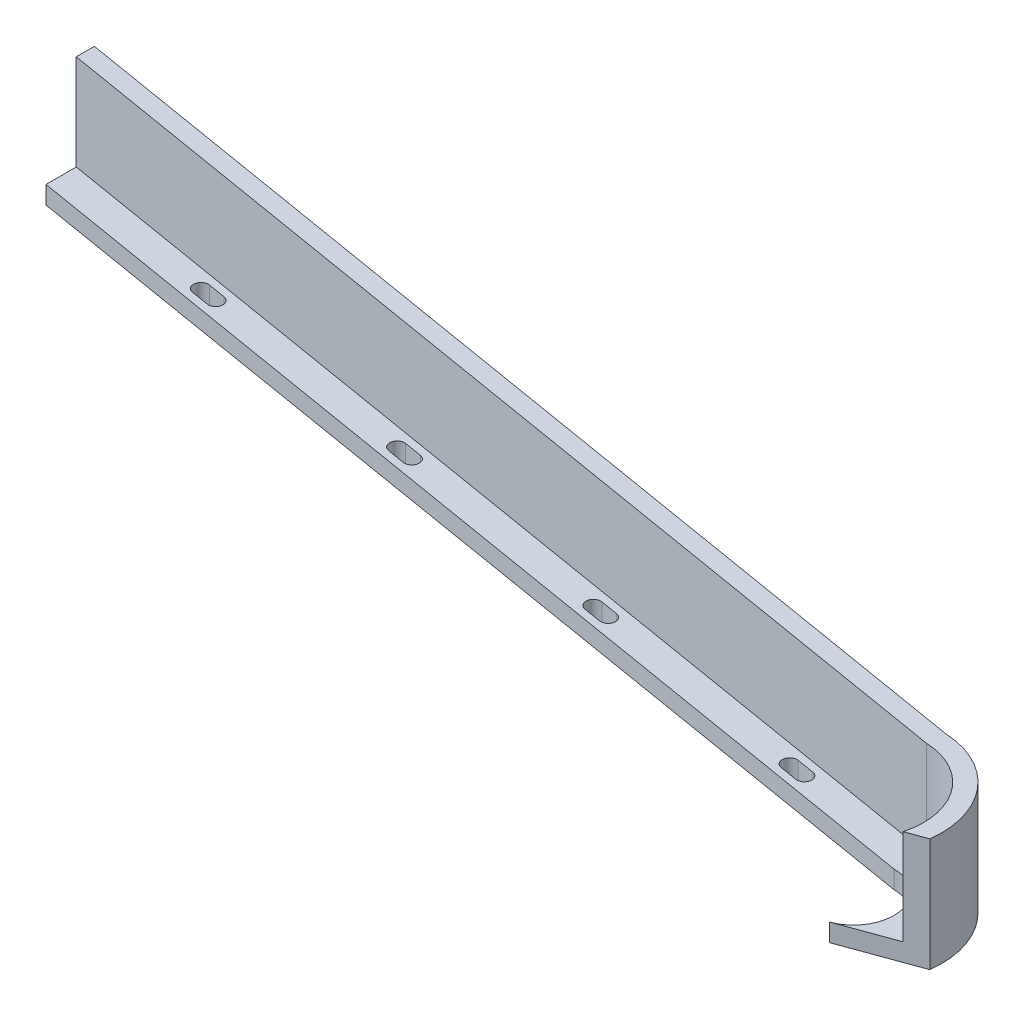
SolidWorks part; units mm, degrees
ref_plane "前视基准面" through (0, 0, 0) normal (0, 0, 1) x (1, 0, 0)
ref_plane "上视基准面" through (0, 0, 0) normal (0, 1, 0) x (1, 0, 0)
ref_plane "右视基准面" through (0, 0, 0) normal (1, 0, 0) x (0, 0, -1)
sketch "草图1" plane through (0, 0, 0) normal (0, 1, 0) x (1, 0, 0)
  line L1 (-17.5, -27.5) -> (17.5, -27.5)
  line L2 (-17.5, -27.5) -> (-17.5, 27.5)
  line L3 (-17.5, 27.5) -> (17.5, 27.5)
  line L4 (17.5, -27.5) -> (17.5, 27.5)
  line L5 (-17.5, -27.5) -> (17.5, 27.5) construction
  line L6 (-17.5, 27.5) -> (17.5, -27.5) construction
  point P0 (0, 0)
  dimension "D1" = 55
  dimension "D2" = 35
extrude "凸台-拉伸1" add sketch "草图1" along normal blind 1
sketch "草图2" plane through (0, 1, 0) normal (0, 1, 0) x (1, 0, 0)
  line L0 (-105.917, 0) -> (-62.25, 0) construction
  line L1 (106.75, 2.25) -> (121.75, 2.25)
  line L2 (-31.4474, 57.1013) -> (151.75, 26.6691)
  line L4 (124.0586, 2.6571) -> (154.0586, 13.5762)
  line L5 (-60.1618, 23.6059) -> (-42.6093, 52.0296)
  line L6 (121.75, 2.25) -> (121.75, 9) construction
  line L7 (121.75, -2.25) -> (121.75, -9) construction
  line L8 (-60.1618, -23.6059) -> (-42.6093, -52.0296)
  line L9 (124.0586, -2.6571) -> (154.0586, -13.5762)
  line L10 (121.75, -9) -> (128.5, -9)
  line L11 (-31.4474, -57.1013) -> (151.75, -26.6691)
  line L12 (106.75, -2.25) -> (121.75, -2.25)
  line L13 (-62.25, 16.25) -> (-62.25, -16.25)
  line L14 (106.75, 2.25) -> (106.75, -2.25)
  line L15 (106.75, 0) -> (124.0666, 0) construction
  arc A0 (-60.1618, 23.6059) -> (-62.25, 16.25) centre (-48.25, 16.25) ccw
  arc A1 (-31.4474, 57.1013) -> (-42.6093, 52.0296) centre (-33.25, 46.25) ccw
  arc A2 (121.75, 2.25) -> (124.0586, 2.6571) centre (121.75, 9) ccw
  arc A3 (154.0586, 13.5762) -> (151.75, 26.6691) centre (151.75, 19.9191) ccw
  arc A4 (154.0586, -13.5762) -> (151.75, -26.6691) centre (151.75, -19.9191) cw
  arc A5 (121.75, -2.25) -> (128.5, -9) centre (121.75, -9) cw
  arc A6 (-31.4474, -57.1013) -> (-42.6093, -52.0296) centre (-33.25, -46.25) cw
  arc A7 (-60.1618, -23.6059) -> (-62.25, -16.25) centre (-48.25, -16.25) cw
  line M10 (17.5, -27.5) -> (17.5, 27.5)
  line M11 (17.5, 27.5) -> (-17.5, 27.5)
  line M12 (-17.5, 27.5) -> (-17.5, -27.5)
  line M13 (-17.5, -27.5) -> (17.5, -27.5)
  dimension "D2" = 28
  dimension "D3" = 48.25
  dimension "D4" = 22
  dimension "D5" = 15
  dimension "D7" = 13.5
  dimension "D10" = 13.5
  dimension "D11" = 30
  dimension "D1" = 2.25
  dimension "D8" = 20
  dimension "D9" = 30
  dimension "D12" = 15
extrude "凸台-拉伸2" add sketch "草图2" along normal blind 3 contours A7 L8 A6 L11 A4 L9 A5 L12 L14 L1 A2 L4 A3 L2 A1 L5 A0 L13 | M13 M10 M11 M12 region at (37.3678, 1, 0) region at (0, 1, 0)
sketch "草图3" plane through (0, 4, 0) normal (0, 1, 0) x (1, 0, 0)
  circle A0 centre (-48.25, 16.25) radius 5
  circle A1 centre (-48.25, -16.25) radius 5
  circle A2 centre (-33.25, 46.25) radius 6.6982
  circle A3 centre (151.75, 19.9191) radius 2.5794
  circle A4 centre (121.75, 9) radius 2.5794
  circle A5 centre (121.75, -9) radius 2.5794
  circle A6 centre (151.75, -19.9191) radius 2.5794
  circle A7 centre (-33.25, -46.25) radius 6.6982
  dimension "D1" = 10
extrude "切除-拉伸1" cut sketch "草图3" against normal through all contours A0 | A1 region at (-48.25, 4, -16.25)
sketch "草图4" plane through (0, 4, 0) normal (0, 1, 0) x (1, 0, 0)
  circle A0 centre (-33.25, 46.25) radius 4
  circle A1 centre (-33.25, -46.25) radius 4
  dimension "D1" = 8
  dimension "D2" = 8
extrude "切除-拉伸2" cut sketch "草图4" against normal blind 2
sketch "草图5" plane through (0, 4, 0) normal (0, 1, 0) x (1, 0, 0)
  circle A0 centre (121.75, 9) radius 2
  circle A1 centre (121.75, -9) radius 2
  circle A2 centre (151.75, 19.9191) radius 2
  circle A3 centre (151.75, -19.9191) radius 2
  dimension "D1" = 4
extrude "切除-拉伸3" cut sketch "草图5" against normal blind 2
sketch "草图8" plane through (0, 1, 0) normal (0, -1, 0) x (1, 0, 0)
  line L1 (-39.75, -26.25) -> (-26.75, -26.25)
  line L2 (-39.75, -26.25) -> (-39.75, -66.25)
  line L3 (-39.75, -66.25) -> (-26.75, -66.25)
  line L4 (-26.75, -26.25) -> (-26.75, -66.25)
  line L5 (-39.75, -26.25) -> (-26.75, -66.25) construction
  line L6 (-39.75, -66.25) -> (-26.75, -26.25) construction
  line L16 (124.0586, 2.6571) -> (154.0586, 13.5762)
  line L17 (151.75, 26.6691) -> (-31.4474, 57.1013)
  line L18 (-42.6093, 52.0296) -> (-60.1618, 23.6059)
  line L19 (-62.25, 16.25) -> (-62.25, -16.25)
  line L20 (-60.1618, -23.6059) -> (-42.6093, -52.0296)
  line L21 (-31.4474, -57.1013) -> (151.75, -26.6691)
  line L22 (154.0586, -13.5762) -> (124.0586, -2.6571)
  line L23 (121.75, -2.25) -> (106.75, -2.25)
  line L24 (106.75, -2.25) -> (106.75, 2.25)
  line L25 (106.75, 2.25) -> (121.75, 2.25)
  line L26 (124.0586, 2.6571) -> (154.0586, 13.5762)
  line L27 (151.75, 26.6691) -> (-31.4474, 57.1013)
  line L28 (-42.6093, 52.0296) -> (-60.1618, 23.6059)
  line L31 (-31.4474, -57.1013) -> (151.75, -26.6691)
  line L32 (154.0586, -13.5762) -> (124.0586, -2.6571)
  line L33 (121.75, -2.25) -> (106.75, -2.25)
  line L34 (106.75, -2.25) -> (106.75, 2.25)
  line L35 (106.75, 2.25) -> (121.75, 2.25)
  arc A8 (154.0586, 13.5762) -> (151.75, 26.6691) centre (151.75, 19.9191) ccw
  arc A9 (-31.4474, 57.1013) -> (-42.6093, 52.0296) centre (-33.25, 46.25) ccw
  arc A10 (-60.1618, 23.6059) -> (-62.25, 16.25) centre (-48.25, 16.25) ccw
  arc A11 (-62.25, -16.25) -> (-60.1618, -23.6059) centre (-48.25, -16.25) ccw
  arc A12 (-42.6093, -52.0296) -> (-31.4474, -57.1013) centre (-33.25, -46.25) ccw
  arc A13 (151.75, -26.6691) -> (154.0586, -13.5762) centre (151.75, -19.9191) ccw
  arc A14 (124.0586, -2.6571) -> (121.75, -2.25) centre (121.75, -9) ccw
  arc A15 (121.75, 2.25) -> (124.0586, 2.6571) centre (121.75, 9) ccw
  arc A16 (154.0586, 13.5762) -> (151.75, 26.6691) centre (151.75, 19.9191) ccw
  arc A17 (-31.4474, 57.1013) -> (-42.6093, 52.0296) centre (-33.25, 46.25) ccw
  arc A18 (-60.1618, 23.6059) -> (-62.25, 16.25) centre (-48.25, 16.25) ccw
  arc A19 (-62.25, -16.25) -> (-60.1618, -23.6059) centre (-48.25, -16.25) ccw
  arc A20 (-42.6093, -52.0296) -> (-31.4474, -57.1013) centre (-33.25, -46.25) ccw
  arc A21 (151.75, -26.6691) -> (154.0586, -13.5762) centre (151.75, -19.9191) ccw
  arc A22 (124.0586, -2.6571) -> (121.75, -2.25) centre (121.75, -9) ccw
  arc A23 (121.75, 2.25) -> (124.0586, 2.6571) centre (121.75, 9) ccw
  point P0 (-33.25, -46.25)
  arc M32 (-42.6093, -52.0296) -> (-31.4474, -57.1013) centre (-33.25, -46.25) ccw
  line M33 (-31.4474, -57.1013) -> (151.75, -26.6691)
  dimension "D1" = 13
  dimension "D2" = 40
  dimension "D3" = 0
extrude "凸台-拉伸3" add sketch "草图8" along normal blind 7 contours L4 L1 L2 M32 M33 region at (-33.2258, 1, -41.4837)
mirror "镜向1" about plane through (0, 0, 0) normal (0, 0, 1) of "凸台-拉伸3"
sketch "草图9" plane through (0, -6, 0) normal (0, -1, 0) x (1, 0, 0)
  line L0 (-39.75, -26.25) -> (-26.75, -26.25) construction
  line L2 (-38.25, -53.75) -> (-38.25, -27.75)
  line L3 (-38.25, -27.75) -> (-28.25, -27.75)
  line L4 (-28.25, -53.75) -> (-28.25, -27.75)
  line L5 (-35.5448, -54.7408) -> (-28.25, -27.75) construction
  line L6 (-38.25, -27.75) -> (-31.223, -53.75) construction
  line L8 (-28.25, -53.75) -> (-38.25, -53.75)
  point P0 (-33.25, -46.25)
  dimension "D1" = 10
  dimension "D2" = 1.5
  dimension "D3" = 26
extrude "切除-拉伸4" cut sketch "草图9" against normal through all from offset 1.5 offset against normal yes
mirror "镜向2" about plane through (0, 0, 0) normal (0, 0, 1) of "切除-拉伸4"
sketch "草图10" plane through (0, 0, -53.75) normal (0, 0, 1) x (1, 0, 0)
  line L4 (-38.25, -4.5) -> (-28.25, -4.5)
  line L5 (-28.25, -4.5) -> (-28.25, 4)
  line L6 (-28.25, 4) -> (-38.25, 4)
  line L7 (-38.25, 4) -> (-38.25, -4.5)
  line L8 (-38.25, -4.5) -> (-28.25, -4.5)
  line L9 (-28.25, -4.5) -> (-28.25, 4)
  line L10 (-28.25, 4) -> (-38.25, 4)
  line L11 (-38.25, 4) -> (-38.25, -4.5)
  circle A0 centre (-33.25, -1.5) radius 1.5
  dimension "D2" = 3
  dimension "D3" = 3
  dimension "D1" = 0
extrude "切除-拉伸5" cut sketch "草图10" against normal through all contours A0 region at (-33.25, -1.5, -53.75)
mirror "镜向3" about plane through (0, 0, 0) normal (0, 0, 1) of "切除-拉伸5"
sketch "草图12" plane through (0, 4, 0) normal (0, 1, 0) x (1, 0, 0)
  line L3 (152.5362, 34.6481) -> (-30.1364, 64.9932)
  line L5 (-42.6093, 52.0296) -> (-60.1618, 23.6059) construction
  line L6 (124.0586, 2.6571) -> (154.0586, 13.5762) construction
  line L10 (154.0586, -13.5762) -> (124.0586, -2.6571)
  line L11 (121.75, -2.25) -> (106.75, -2.25)
  line L12 (106.75, -2.25) -> (106.75, 2.25)
  line L13 (106.75, 2.25) -> (121.75, 2.25)
  line L14 (124.0586, 2.6571) -> (154.0586, 13.5762)
  line L15 (151.75, 26.6691) -> (-31.4474, 57.1013)
  line L16 (-42.6093, 52.0296) -> (-60.1618, 23.6059)
  line L17 (-62.25, 16.25) -> (-62.25, -16.25)
  line L18 (-60.1618, -23.6059) -> (-42.6093, -52.0296)
  line L19 (-31.4474, -57.1013) -> (151.75, -26.6691)
  line L23 (-62.25, 2.25) -> (121.75, 2.25)
  line L24 (124.0586, 2.6571) -> (166.3826, 18.0617)
  line L26 (-34.4695, 65.2108) -> (-60.1618, 23.6059)
  line L27 (-62.25, 16.25) -> (-62.25, 2.25)
  line L30 (-49.416, 56.233) -> (-66.9685, 27.8093) construction
  line L31 (-70.25, 16.25) -> (-70.25, -5.75) construction
  line L32 (-70.25, -5.75) -> (121.75, -5.75) construction
  line L33 (126.7948, -4.8605) -> (156.7948, 6.0586) construction
  line L34 (151.75, 26.6691) -> (-31.4474, 57.1013) construction
  arc A1 (166.3826, 18.0617) -> (152.5362, 34.6481) centre (151.75, 19.9191) ccw
  arc A2 (-30.1364, 64.9932) -> (-34.4695, 65.2108) centre (-33.25, 46.25) ccw
  arc A4 (-30.1364, 64.9932) -> (-49.416, 56.233) centre (-33.25, 46.25) ccw construction
  arc A5 (156.7948, 6.0586) -> (152.5362, 34.6481) centre (151.75, 19.9191) ccw construction
  arc A8 (124.0586, -2.6571) -> (121.75, -2.25) centre (121.75, -9) ccw
  arc A9 (121.75, 2.25) -> (124.0586, 2.6571) centre (121.75, 9) ccw
  arc A10 (154.0586, 13.5762) -> (151.75, 26.6691) centre (151.75, 19.9191) ccw
  arc A11 (-31.4474, 57.1013) -> (-42.6093, 52.0296) centre (-33.25, 46.25) ccw
  arc A12 (-60.1618, 23.6059) -> (-62.25, 16.25) centre (-48.25, 16.25) ccw
  arc A13 (-62.25, -16.25) -> (-60.1618, -23.6059) centre (-48.25, -16.25) ccw
  arc A14 (-42.6093, -52.0296) -> (-31.4474, -57.1013) centre (-33.25, -46.25) ccw
  arc A15 (151.75, -26.6691) -> (154.0586, -13.5762) centre (151.75, -19.9191) ccw
  arc A17 (121.75, 2.25) -> (124.0586, 2.6571) centre (121.75, 9) ccw
  arc A20 (-60.1618, 23.6059) -> (-62.25, 16.25) centre (-48.25, 16.25) ccw
  arc A24 (-66.9685, 27.8093) -> (-70.25, 16.25) centre (-48.25, 16.25) ccw construction
  arc A25 (121.75, -5.75) -> (126.7948, -4.8605) centre (121.75, 9) ccw construction
  arc A26 (-31.4474, 57.1013) -> (-42.6093, 52.0296) centre (-33.25, 46.25) ccw construction
  arc A27 (154.0586, 13.5762) -> (151.75, 26.6691) centre (151.75, 19.9191) ccw construction
  dimension "D1" = 0
  dimension "D2" = 8
extrude "凸台-拉伸4" add sketch "草图12" along normal blind 3
sketch "草图13" plane through (0, 4, 0) normal (0, -1, 0) x (1, 0, 0)
  line L1 (-119.1699, 86.8947) -> (214.8426, 86.8947)
  line L2 (-119.1699, 86.8947) -> (-119.1699, -74.5615)
  line L3 (-119.1699, -74.5615) -> (214.8426, -74.5615)
  line L4 (214.8426, 86.8947) -> (214.8426, -74.5615)
  line L5 (-119.1699, 86.8947) -> (214.8426, -74.5615) construction
  line L6 (-119.1699, -74.5615) -> (214.8426, 86.8947) construction
  point P0 (47.8363, 6.1666)
extrude "切除-拉伸6" cut sketch "草图13" along normal blind 10
sketch "草图14" plane through (0, 4, 0) normal (0, -1, 0) x (1, 0, 0)
  circle A0 centre (151.75, -19.9191) radius 3.5
  circle A1 centre (121.75, -9) radius 3.5
  dimension "D2" = 7
  dimension "D3" = 7
extrude "切除-拉伸7" cut sketch "草图14" against normal blind 2.5
sketch "草图15" plane through (0, 4, 0) normal (0, -1, 0) x (1, 0, 0)
  circle A0 centre (-48.25, -16.25) radius 5
  dimension "D1" = 10
extrude "切除-拉伸8" cut sketch "草图15" against normal through all
sketch "草图17" plane through (0, 4, 0) normal (0, -1, 0) x (1, 0, 0)
  line L0 (-30.6281, -62.0337) -> (152.2188, -31.6598)
  line L1 (-34.4695, -65.2108) -> (-36.5044, -61.9155)
  line L3 (166.3826, -18.0617) -> (163.0963, -16.8656)
  line L5 (166.3826, -18.0617) -> (124.0586, -2.6571)
  line L6 (121.75, -2.25) -> (-62.25, -2.25)
  line L7 (-62.25, -2.25) -> (-62.25, -16.25)
  line L8 (-60.1618, -23.6059) -> (-34.4695, -65.2108)
  line L9 (-30.1364, -64.9932) -> (152.5362, -34.6481)
  line L14 (-30.1364, -64.9932) -> (152.5362, -34.6481)
  arc A0 (-36.5044, -61.9155) -> (-30.6281, -62.0337) centre (-33.25, -46.25) ccw
  arc A1 (152.2188, -31.6598) -> (163.0963, -16.8656) centre (151.75, -19.9191) ccw
  arc A2 (-34.2769, -62.217) -> (-30.6281, -62.0337) centre (-33.25, -46.25) ccw construction
  arc A3 (152.2188, -31.6598) -> (163.4065, -18.4395) centre (151.75, -19.9191) ccw construction
  arc A4 (124.0586, -2.6571) -> (121.75, -2.25) centre (121.75, -9) ccw
  arc A5 (-62.25, -16.25) -> (-60.1618, -23.6059) centre (-48.25, -16.25) ccw
  arc A6 (-34.4695, -65.2108) -> (-30.1364, -64.9932) centre (-33.25, -46.25) ccw
  arc A7 (152.5362, -34.6481) -> (166.3826, -18.0617) centre (151.75, -19.9191) ccw
  arc A10 (-34.4695, -65.2108) -> (-30.1364, -64.9932) centre (-33.25, -46.25) ccw
  arc A11 (152.5362, -34.6481) -> (166.3826, -18.0617) centre (151.75, -19.9191) ccw
  dimension "D1" = 0
  dimension "D2" = 3
extrude "凸台-拉伸5" add sketch "草图17" along normal blind 16
sketch "草图18" plane through (0, 7, 0) normal (0, 1, 0) x (1, 0, 0)
  line L1 (-39.75, 26.25) -> (-26.75, 26.25)
  line L2 (-39.75, 26.25) -> (-39.75, 56.6598)
  line L4 (-26.75, 26.25) -> (-26.75, 64.4306)
  line L5 (-39.75, 26.25) -> (-27.311, 64.5238) construction
  line L6 (-37.7079, 59.9667) -> (-26.75, 26.25) construction
  line L11 (-62.25, 16.25) -> (-62.25, 2.25)
  line L12 (-62.25, 2.25) -> (121.75, 2.25)
  line L13 (124.0586, 2.6571) -> (166.3826, 18.0617)
  line L14 (152.5362, 34.6481) -> (-30.1364, 64.9932)
  line L15 (-34.4695, 65.2108) -> (-60.1618, 23.6059)
  line L19 (-26.75, 64.4306) -> (-30.1364, 64.9932)
  line L20 (-34.4695, 65.2108) -> (-39.75, 56.6598)
  arc A0 (-30.1364, 64.9932) -> (-34.4695, 65.2108) centre (-33.25, 46.25) ccw construction
  arc A1 (-30.1364, 64.9932) -> (-34.4695, 65.2108) centre (-33.25, 46.25) ccw
  arc A6 (121.75, 2.25) -> (124.0586, 2.6571) centre (121.75, 9) ccw
  arc A7 (166.3826, 18.0617) -> (152.5362, 34.6481) centre (151.75, 19.9191) ccw
  arc A8 (-30.1364, 64.9932) -> (-34.4695, 65.2108) centre (-33.25, 46.25) ccw
  arc A9 (-60.1618, 23.6059) -> (-62.25, 16.25) centre (-48.25, 16.25) ccw
  arc A10 (121.75, 2.25) -> (124.0586, 2.6571) centre (121.75, 9) ccw
  arc A12 (-30.1364, 64.9932) -> (-34.4695, 65.2108) centre (-33.25, 46.25) ccw
  line M18 (152.5362, 34.6481) -> (-30.1364, 64.9932)
  arc M19 (-30.1364, 64.9932) -> (-34.4695, 65.2108) centre (-33.25, 46.25) ccw
  line M20 (-34.4695, 65.2108) -> (-60.1618, 23.6059)
  dimension "D3" = 0
extrude "凸台-拉伸6" add sketch "草图18" along normal blind 7 contours L1 L4 L2 M18 M19 M20 region at (-33.0469, 7, -44.8798)
sketch "草图19" plane through (0, 14, 0) normal (0, 1, 0) x (1, 0, 0)
  line L5 (-38.25, 53.75) -> (-28.25, 53.75)
  line L8 (-38.25, 27.75) -> (-28.25, 27.75)
  line L9 (-28.25, 64.75) -> (-28.25, 64.6798)
  line L10 (-39.75, 26.25) -> (-26.75, 26.25)
  line L11 (-26.75, 26.25) -> (-26.75, 64.4306)
  line L12 (-26.75, 64.4306) -> (-30.1364, 64.9932)
  line L13 (-34.4695, 65.2108) -> (-39.75, 56.6598)
  line L14 (-39.75, 56.6598) -> (-39.75, 26.25)
  line L17 (-26.75, 64.4306) -> (-28.6727, 64.75)
  line L18 (-34.4695, 65.2108) -> (-34.754, 64.75)
  line L21 (-38.25, 27.75) -> (-31.223, 53.75) construction
  line L22 (-38.25, 53.75) -> (-38.25, 27.75)
  line L23 (-35.277, 53.75) -> (-28.25, 27.75) construction
  line L24 (-28.2682, 64.6828) -> (-28.25, 64.75) construction
  line L25 (-28.25, 53.75) -> (-28.25, 27.75)
  line L27 (-28.6727, 64.75) -> (-28.25, 64.75)
  arc A2 (-30.1364, 64.9932) -> (-34.4695, 65.2108) centre (-33.25, 46.25) ccw
  dimension "D2" = 10
  dimension "D4" = 26
  dimension "D1" = 0
extrude "切除-拉伸9" cut sketch "草图19" against normal through all from offset 1.5 contours L25 L5 L22 L8 region at (-33.25, 14, -40.75) offset against normal yes
sketch "草图20" plane through (0, 0, -53.75) normal (0, 0, 1) x (1, 0, 0)
  line L4 (-38.25, 4) -> (-28.25, 4)
  line L5 (-28.25, 4) -> (-28.25, 12.5)
  line L6 (-28.25, 12.5) -> (-38.25, 12.5)
  line L7 (-38.25, 12.5) -> (-38.25, 4)
  line L8 (-38.25, 4) -> (-28.25, 4)
  line L9 (-28.25, 4) -> (-28.25, 12.5)
  line L10 (-28.25, 12.5) -> (-38.25, 12.5)
  line L11 (-38.25, 12.5) -> (-38.25, 4)
  circle A0 centre (-33.25, 9.5) radius 1.5
  dimension "D2" = 3
  dimension "D3" = 3
  dimension "D1" = 0
extrude "切除-拉伸10" cut sketch "草图20" against normal through all contours A0 region at (-33.25, 9.5, -53.75)
thread "螺纹线1" pitch 0.6 method cut profile "螺纹线轮廓1" start angle 0, offset 0, length 15, pitch 0.6, diameter 3
ref_plane "基准面1" through (-34.75, 9.5, -53.75) normal (0, -1, 0) x (-1, 0, 0)
sketch "螺纹线轮廓1" plane through (-34.75, 9.5, -53.75) normal (0, -1, 0) x (-1, 0, 0)
  line L0 (0, 0) -> (0, 0.6) construction
  line L1 (0, 0) -> (0.3248, 0.1875)
  line L2 (0.3248, 0.1875) -> (0.3248, 0.2625)
  line L3 (0.3248, 0.2625) -> (0, 0.45)
  line L4 (0.3248, 0.225) -> (0, 0.225) construction
  line L11 (0, 0) -> (0, 0.45)
  point P2 (0, 0)
  dimension "Pitch" = 0.6
  dimension "Profile_Angle" = 60
  dimension "Profile_Land" = 0.075
  dimension "Profile_Height" = 0.3248
sketch "草图21" plane through (0, 14, 0) normal (0, 1, 0) x (1, 0, 0)
  line L0 (-38.25, 27.75) -> (-28.25, 27.75) construction
  line L1 (-39.75, 27.75) -> (-26.75, 27.75)
  line L5 (-39.75, 26.25) -> (-26.75, 26.25)
  line L6 (-26.75, 26.25) -> (-26.75, 64.4306)
  line L7 (-26.75, 64.4306) -> (-30.1364, 64.9932)
  line L8 (-34.4695, 65.2108) -> (-39.75, 56.6598)
  line L9 (-39.75, 56.6598) -> (-39.75, 26.25)
  line L11 (-26.75, 27.75) -> (-26.75, 64.4306)
  line L12 (-26.75, 64.4306) -> (-30.1364, 64.9932)
  line L13 (-34.4695, 65.2108) -> (-39.75, 56.6598)
  line L14 (-39.75, 56.6598) -> (-39.75, 27.75)
  arc A1 (-30.1364, 64.9932) -> (-34.4695, 65.2108) centre (-33.25, 46.25) ccw
  arc A2 (-30.1364, 64.9932) -> (-34.4695, 65.2108) centre (-33.25, 46.25) ccw
  dimension "D1" = 0
extrude "切除-拉伸11" cut sketch "草图21" against normal through all
sketch "草图22" plane through (0, 14, 0) normal (0, 1, 0) x (1, 0, 0)
  line L4 (-26.75, 27.75) -> (-39.75, 27.75)
  line L5 (-39.75, 27.75) -> (-39.75, 26.25)
  line L6 (-39.75, 26.25) -> (-26.75, 26.25)
  line L7 (-26.75, 26.25) -> (-26.75, 27.75)
  line L8 (-26.75, 27.75) -> (-39.75, 27.75)
  line L9 (-39.75, 27.75) -> (-39.75, 26.25)
  line L10 (-39.75, 26.25) -> (-26.75, 26.25)
  line L11 (-26.75, 26.25) -> (-26.75, 27.75)
  dimension "D1" = 0
extrude "切除-拉伸12" cut sketch "草图22" against normal up to surface (7 mm away) up to face at (-48.25, 7, -21.25)
sketch "草图23" plane through (0, 7, 0) normal (0, 1, 0) x (1, 0, 0)
  line L0 (-45.75, 27.75) -> (-20.75, 27.75)
  line L1 (-20.75, 27.75) -> (-18.75, 27.75)
  line L2 (-18.75, 63.1017) -> (-18.75, 2.25)
  line L8 (-26.75, 64.4306) -> (-26.75, 27.75)
  line L9 (-26.75, 27.75) -> (-39.75, 27.75)
  line L10 (-39.75, 27.75) -> (-39.75, 56.6598)
  line L11 (-39.75, 56.6598) -> (-60.1618, 23.6059)
  line L12 (-62.25, 16.25) -> (-62.25, 2.25)
  line L13 (-62.25, 2.25) -> (121.75, 2.25)
  line L14 (124.0586, 2.6571) -> (166.3826, 18.0617)
  line L15 (152.5362, 34.6481) -> (-26.75, 64.4306)
  line L16 (-26.75, 64.4306) -> (-26.75, 27.75)
  line L17 (-26.75, 27.75) -> (-39.75, 27.75)
  line L18 (-39.75, 27.75) -> (-39.75, 56.6598)
  line L19 (-39.75, 56.6598) -> (-60.1618, 23.6059)
  line L20 (-62.25, 16.25) -> (-62.25, 2.25)
  line L21 (-62.25, 2.25) -> (-18.75, 2.25)
  line L23 (-18.75, 63.1017) -> (-26.75, 64.4306)
  circle A0 centre (-48.25, 16.25) radius 5 construction
  circle A1 centre (-48.25, 16.25) radius 5
  arc A3 (-60.1618, 23.6059) -> (-62.25, 16.25) centre (-48.25, 16.25) ccw
  arc A4 (121.75, 2.25) -> (124.0586, 2.6571) centre (121.75, 9) ccw
  arc A5 (166.3826, 18.0617) -> (152.5362, 34.6481) centre (151.75, 19.9191) ccw
  arc A6 (-60.1618, 23.6059) -> (-62.25, 16.25) centre (-48.25, 16.25) ccw
  point P13 (-33.25, 27.75)
  line M14 (-26.75, 64.4306) -> (-26.75, 27.75)
  line M15 (-26.75, 27.75) -> (-39.75, 27.75)
  line M16 (-39.75, 27.75) -> (-39.75, 56.6598)
  line M17 (-39.75, 56.6598) -> (-60.1618, 23.6059)
  arc M18 (-60.1618, 23.6059) -> (-62.25, 16.25) centre (-48.25, 16.25) ccw
  line M19 (-62.25, 16.25) -> (-62.25, 2.25)
  line M20 (-62.25, 2.25) -> (121.75, 2.25)
  line M24 (152.5362, 34.6481) -> (-26.75, 64.4306)
  circle M25 centre (-48.25, 16.25) radius 5
  dimension "D2" = 25
  dimension "D3" = 2
  dimension "D1" = 0
extrude "凸台-拉伸7" add sketch "草图23" along normal blind 2 contours L2 L1 L0 M15 M16 M17 M18 M19 M20 M25 | L2 L0 L1 M24 M14 region at (-40.7754, 7, -19.3253) region at (-22.7746, 7, -45.7601)
sketch "草图24" plane through (0, 9, 0) normal (0, 1, 0) x (1, 0, 0)
  line L0 (-45.75, 27.75) -> (-20.75, 27.75)
  line L1 (-45.75, 27.75) -> (-45.75, 46.9437)
  line L2 (-39.75, 56.6598) -> (-60.1618, 23.6059) construction
  line L3 (-20.75, 27.75) -> (-20.75, 86.4202)
  line L4 (-20.75, 86.4202) -> (-45.75, 86.4202)
  line L5 (-45.75, 86.4202) -> (-45.75, 46.0349)
  point P3 (-33.25, 27.75)
  line M3 (-39.75, 27.75) -> (-39.75, 56.6598)
  line M4 (-39.75, 56.6598) -> (-60.1618, 23.6059)
  line M9 (-18.75, 63.1017) -> (-26.75, 64.4306)
  line M10 (-26.75, 64.4306) -> (-26.75, 27.75)
  dimension "D1" = 25
extrude "切除-拉伸15" cut sketch "草图24" against normal through all from offset 3 contours L1 L0 M3 M4 | L0 L3 M9 M10 region at (-42.548, 9, -39.9394) region at (-23.7638, 9, -45.8423) offset against normal yes
sketch "草图25" plane through (0, 4, 0) normal (0, -1, 0) x (1, 0, 0)
  circle A0 centre (-48.25, -16.25) radius 7.5
  dimension "D1" = 15
extrude "切除-拉伸16" cut sketch "草图25" against normal blind 4
sketch "草图26" plane through (0, 7, 0) normal (0, 1, 0) x (1, 0, 0)
  line L0 (-48.25, 16.25) -> (51.3855, 16.25)
  line L1 (1.75, 16.25) -> (5.75, 16.25) construction
  line L2 (1.75, 18) -> (5.75, 18)
  line L3 (1.75, 14.5) -> (5.75, 14.5)
  line L4 (41.75, 16.25) -> (45.75, 16.25) construction
  line L5 (41.75, 18) -> (45.75, 18)
  line L6 (41.75, 14.5) -> (45.75, 14.5)
  line L7 (81.75, 16.25) -> (85.75, 16.25) construction
  line L8 (81.75, 18) -> (85.75, 18)
  line L9 (81.75, 14.5) -> (85.75, 14.5)
  line L10 (1.75, 31.25) -> (1.75, 35.25) construction
  line L11 (0, 31.25) -> (0, 35.25)
  line L12 (3.5, 31.25) -> (3.5, 35.25)
  arc A0 (1.75, 18) -> (1.75, 14.5) centre (1.75, 16.25) ccw
  arc A1 (5.75, 14.5) -> (5.75, 18) centre (5.75, 16.25) ccw
  arc A2 (41.75, 18) -> (41.75, 14.5) centre (41.75, 16.25) ccw
  arc A3 (45.75, 14.5) -> (45.75, 18) centre (45.75, 16.25) ccw
  arc A4 (81.75, 18) -> (81.75, 14.5) centre (81.75, 16.25) ccw
  arc A5 (85.75, 14.5) -> (85.75, 18) centre (85.75, 16.25) ccw
  arc A6 (0, 31.25) -> (3.5, 31.25) centre (1.75, 31.25) ccw
  arc A7 (3.5, 35.25) -> (0, 35.25) centre (1.75, 35.25) ccw
  point P5 (3.75, 16.25)
  point P10 (43.75, 16.25)
  point P17 (83.75, 16.25)
  point P24 (3.75, 14.5)
  point P27 (1.75, 33.25)
  dimension "D1" = 3.5
  dimension "D2" = 4
  dimension "D3" = 40
  dimension "D4" = 40
  dimension "D5" = 50
  dimension "D6" = 15
extrude "切除-拉伸17" cut sketch "草图26" against normal blind 10 contours L12 A7 L11 A6 | L0 A3 L5 A2 | L6 A3 L0 A2 | L9 A5 L8 A4 | L2 A1 L3 A0 region at (43.75, 7, -17.0711) region at (43.75, 7, -15.4289) region at (83.75, 7, -16.25) region at (1.75, 7, -33.25)
sketch "草图27" plane through (0, 6, 0) normal (0, -1, 0) x (1, 0, 0)
  line L0 (-26.75, -27.75) -> (-20.75, -27.75)
  line L1 (-45.75, -27.75) -> (-39.75, -27.75)
  line L2 (-45.75, -27.75) -> (-39.75, -27.75) construction
  circle A0 centre (-23.75, -32.75) radius 1.75
  circle A1 centre (-23.75, -42.75) radius 1.75
  circle A2 centre (-42.75, -32.75) radius 1.75
  circle A3 centre (-42.75, -42.75) radius 1.75
  dimension "D1" = 3.5
  dimension "D4" = 10
  dimension "D5" = 10
  dimension "D2" = 5
  dimension "D3" = 5
extrude "切除-拉伸18" cut sketch "草图27" against normal blind 10 contours A2 | A3 | A0 | A1 region at (-23.75, 6, -32.75) region at (-42.75, 6, -32.75) region at (-42.75, 6, -42.75)
sketch "草图28" plane through (0, 9, 0) normal (0, 1, 0) x (1, 0, 0)
  line L8 (-26.75, 27.75) -> (-39.75, 27.75)
  line L9 (-39.75, 27.75) -> (-39.75, 56.6598)
  line L10 (-39.75, 56.6598) -> (-60.1618, 23.6059)
  line L11 (-62.25, 16.25) -> (-62.25, 2.25)
  line L12 (-62.25, 2.25) -> (-18.75, 2.25)
  line L13 (-18.75, 2.25) -> (-18.75, 63.1017)
  line L14 (-18.75, 63.1017) -> (-26.75, 64.4306)
  line L15 (-26.75, 64.4306) -> (-26.75, 27.75)
  line L16 (-26.75, 27.75) -> (-39.75, 27.75)
  line L17 (-39.75, 27.75) -> (-39.75, 56.6598)
  line L18 (-39.75, 56.6598) -> (-60.1618, 23.6059)
  line L19 (-62.25, 16.25) -> (-62.25, 2.25)
  line L20 (-62.25, 2.25) -> (-18.75, 2.25)
  line L21 (-18.75, 2.25) -> (-18.75, 63.1017)
  line L22 (-18.75, 63.1017) -> (-26.75, 64.4306)
  line L23 (-26.75, 64.4306) -> (-26.75, 27.75)
  arc A1 (-60.1618, 23.6059) -> (-62.25, 16.25) centre (-48.25, 16.25) ccw
  arc A2 (-60.1618, 23.6059) -> (-62.25, 16.25) centre (-48.25, 16.25) ccw
  dimension "D1" = 0
extrude "切除-拉伸19" cut sketch "草图28" against normal through all
sketch "草图29" plane through (0, 4, 0) normal (0, -1, 0) x (1, 0, 0)
  line L0 (-18.75, -54.992) -> (151.75, -26.6691)
  line L4 (121.75, -2.25) -> (-18.75, -2.25)
  line L5 (-18.75, -2.25) -> (-18.75, -60.0606)
  line L6 (-18.75, -60.0606) -> (152.2188, -31.6598)
  line L7 (163.0963, -16.8656) -> (124.0586, -2.6571)
  line L8 (121.75, -2.25) -> (-18.75, -2.25)
  line L9 (-18.75, -2.25) -> (-18.75, -60.0606)
  line L10 (-18.75, -60.0606) -> (152.2188, -31.6598)
  line L11 (163.0963, -16.8656) -> (124.0586, -2.6571)
  line L12 (-13.75, -54.1615) -> (151.75, -26.6691) construction
  line L17 (158.4746, -20.5043) -> (122.3485, -7.3555) construction
  line L18 (121.75, -7.25) -> (-13.75, -7.25) construction
  line L19 (-13.75, -7.25) -> (-13.75, -54.1615) construction
  arc A0 (151.75, -26.6691) -> (154.0586, -13.5762) centre (151.75, -19.9191) ccw
  arc A2 (152.2188, -31.6598) -> (163.0963, -16.8656) centre (151.75, -19.9191) ccw
  arc A3 (124.0586, -2.6571) -> (121.75, -2.25) centre (121.75, -9) ccw
  arc A4 (152.2188, -31.6598) -> (163.0963, -16.8656) centre (151.75, -19.9191) ccw
  arc A5 (124.0586, -2.6571) -> (121.75, -2.25) centre (121.75, -9) ccw
  arc A6 (151.75, -26.6691) -> (158.4746, -20.5043) centre (151.75, -19.9191) ccw construction
  arc A9 (122.3485, -7.3555) -> (121.75, -7.25) centre (121.75, -9) ccw construction
  arc M7 (0, -31.25) -> (3.5, -31.25) centre (1.75, -31.25) cw
  line M8 (3.5, -31.25) -> (3.5, -35.25)
  arc M9 (3.5, -35.25) -> (0, -35.25) centre (1.75, -35.25) cw
  line M10 (0, -35.25) -> (0, -31.25)
  line M11 (45.75, -18) -> (41.75, -18)
  arc M12 (41.75, -18) -> (41.75, -14.5) centre (41.75, -16.25) cw
  line M13 (41.75, -14.5) -> (45.75, -14.5)
  arc M14 (45.75, -14.5) -> (45.75, -18) centre (45.75, -16.25) cw
  arc M15 (81.75, -18) -> (81.75, -14.5) centre (81.75, -16.25) cw
  line M16 (81.75, -14.5) -> (85.75, -14.5)
  arc M17 (85.75, -14.5) -> (85.75, -18) centre (85.75, -16.25) cw
  line M18 (85.75, -18) -> (81.75, -18)
  line M19 (5.75, -18) -> (1.75, -18)
  arc M20 (1.75, -18) -> (1.75, -14.5) centre (1.75, -16.25) cw
  line M21 (1.75, -14.5) -> (5.75, -14.5)
  arc M22 (5.75, -14.5) -> (5.75, -18) centre (5.75, -16.25) cw
  circle M23 centre (121.75, -9) radius 3.5
  circle M24 centre (151.75, -19.9191) radius 3.5
  line M25 (121.75, -2.25) -> (-18.75, -2.25)
  line M26 (-18.75, -2.25) -> (-18.75, -60.0606)
  arc M30 (124.0586, -2.6571) -> (121.75, -2.25) centre (121.75, -9) ccw
  dimension "D1" = 0
  dimension "D2" = 5
extrude "切除-拉伸23" cut sketch "草图29" against normal blind 10 contours L0 A0 L11 M30 M25 M26 M24 M23 M22 M19 M20 M21 M18 M15 M16 M17 M14 M11 M12 M13 M10 M7 M8 M9 | M23 | M24 region at (54.4927, 4, -22.9012) region at (121.75, 4, -9) region at (151.75, 4, -19.9191)
sketch "草图30" plane through (0, 4, 0) normal (0, -1, 0) x (1, 0, 0)
  line L1 (9.3647, -52.856) -> (12.3242, -52.3644) construction
  line L2 (151.8091, -29.1935) -> (-19.1597, -57.5944)
  line L3 (151.8091, -29.1935) -> (-18.75, -57.5263)
  line L4 (9.1599, -51.6229) -> (12.1193, -51.1313)
  line L5 (9.5696, -54.0891) -> (12.529, -53.5975)
  line L6 (48.824, -46.3011) -> (51.7834, -45.8095) construction
  line L7 (48.6192, -45.068) -> (51.5786, -44.5764)
  line L8 (49.0288, -47.5342) -> (51.9883, -47.0426)
  line L9 (88.2833, -39.7463) -> (91.2427, -39.2547) construction
  line L10 (88.0784, -38.5132) -> (91.0379, -38.0215)
  line L11 (88.4881, -40.9794) -> (91.4476, -40.4878)
  line L12 (127.7425, -33.1914) -> (130.702, -32.6998) construction
  line L13 (127.5377, -31.9583) -> (130.4971, -31.4667)
  line L14 (127.9474, -34.4245) -> (130.9068, -33.9329)
  line L15 (-18.75, -54.992) -> (-18.75, -60.0606) construction
  line L16 (-18.75, -54.992) -> (-18.75, -60.0606)
  arc A0 (9.1599, -51.6229) -> (9.5696, -54.0891) centre (9.3647, -52.856) ccw
  arc A1 (12.529, -53.5975) -> (12.1193, -51.1313) centre (12.3242, -52.3644) ccw
  arc A2 (48.6192, -45.068) -> (49.0288, -47.5342) centre (48.824, -46.3011) ccw
  arc A3 (51.9883, -47.0426) -> (51.5786, -44.5764) centre (51.7834, -45.8095) ccw
  arc A4 (88.0784, -38.5132) -> (88.4881, -40.9794) centre (88.2833, -39.7463) ccw
  arc A5 (91.4476, -40.4878) -> (91.0379, -38.0215) centre (91.2427, -39.2547) ccw
  arc A6 (127.5377, -31.9583) -> (127.9474, -34.4245) centre (127.7425, -33.1914) ccw
  arc A7 (130.9068, -33.9329) -> (130.4971, -31.4667) centre (130.702, -32.6998) ccw
  point P2 (10.8445, -52.6102)
  point P9 (10.6396, -51.3771)
  point P12 (50.3037, -46.0553)
  point P17 (89.763, -39.5005)
  point P26 (129.2223, -32.9456)
  dimension "D2" = 2.5
  dimension "D3" = 3
  dimension "D4" = 40
  dimension "D5" = 40
  dimension "D6" = 40
  dimension "D7" = 30
  dimension "D1" = 2.5
extrude "切除-拉伸24" cut sketch "草图30" against normal blind 10 contours L5 A1 L4 A0 | L8 A3 L7 A2 | L11 A5 L10 A4 | L14 A7 L13 A6
sketch "草图31" plane through (0, -12, 0) normal (0, -1, 0) x (1, 0, 0)
  line L4 (-18.75, -60.0606) -> (-18.75, -63.1017)
  line L5 (-18.75, -63.1017) -> (152.5362, -34.6481)
  line L6 (166.3826, -18.0617) -> (163.0963, -16.8656)
  line L7 (152.2188, -31.6598) -> (-18.75, -60.0606)
  line L8 (-18.75, -60.0606) -> (-18.75, -63.1017)
  line L9 (-18.75, -63.1017) -> (152.5362, -34.6481)
  line L10 (166.3826, -18.0617) -> (163.0963, -16.8656)
  line L11 (152.2188, -31.6598) -> (-18.75, -60.0606)
  arc A2 (152.5362, -34.6481) -> (166.3826, -18.0617) centre (151.75, -19.9191) ccw
  arc A3 (152.2188, -31.6598) -> (163.0963, -16.8656) centre (151.75, -19.9191) ccw
  arc A4 (152.5362, -34.6481) -> (166.3826, -18.0617) centre (151.75, -19.9191) ccw
  arc A5 (152.2188, -31.6598) -> (163.0963, -16.8656) centre (151.75, -19.9191) ccw
  dimension "D1" = 0
extrude "凸台-拉伸8" add sketch "草图31" against normal blind 16 from surface starting at face at (10.8445, 7, -52.6102)
sketch "草图32" plane through (0, -12, 0) normal (0, -1, 0) x (1, 0, 0)
  line L4 (-18.75, -60.0606) -> (-18.75, -63.1017)
  line L5 (-18.75, -63.1017) -> (152.5362, -34.6481)
  line L6 (166.3826, -18.0617) -> (163.0963, -16.8656)
  line L7 (152.2188, -31.6598) -> (-18.75, -60.0606)
  line L8 (-18.75, -60.0606) -> (-18.75, -63.1017)
  line L9 (-18.75, -63.1017) -> (152.5362, -34.6481)
  line L10 (166.3826, -18.0617) -> (163.0963, -16.8656)
  line L11 (152.2188, -31.6598) -> (-18.75, -60.0606)
  arc A2 (152.5362, -34.6481) -> (166.3826, -18.0617) centre (151.75, -19.9191) ccw
  arc A3 (152.2188, -31.6598) -> (163.0963, -16.8656) centre (151.75, -19.9191) ccw
  arc A4 (152.5362, -34.6481) -> (166.3826, -18.0617) centre (151.75, -19.9191) ccw
  arc A5 (152.2188, -31.6598) -> (163.0963, -16.8656) centre (151.75, -19.9191) ccw
  dimension "D1" = 0
extrude "切除-拉伸25" cut sketch "草图32" against normal up to surface (16 mm away) up to face at (10.8445, 4, -52.6102)
